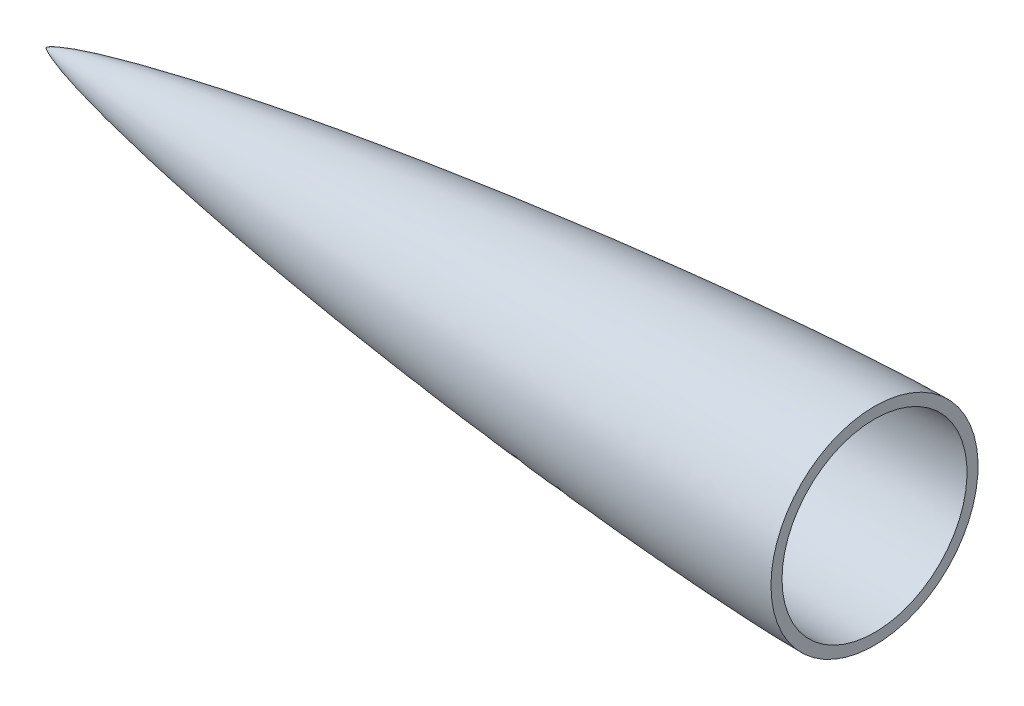
SolidWorks part; units mm, degrees
material "Rocket Fibreglass"
ref_plane "Front Plane" through (0, 0, 0) normal (0, 0, 1) x (1, 0, 0)
ref_plane "Top Plane" through (0, 0, 0) normal (0, 1, 0) x (1, 0, 0)
ref_plane "Right Plane" through (0, 0, 0) normal (1, 0, 0) x (0, 0, -1)
sketch "Sketch3" plane through (0, 0, 0) normal (0, 0, 1) x (1, 0, 0)
  line L0 (0, 0) -> (300, 0)
  line L1 (300, 0) -> (300, 37.5)
  spline S0 degree 4 poles (0, 0) (0.002, 0.0062) (0.0071, 0.018) (0.0217, 0.0396) (0.0552, 0.0792) (0.1042, 0.126) (0.1683, 0.1794) (0.2608, 0.2488) (0.3875, 0.3348) (0.5786, 0.4525) (0.8976, 0.6294) (1.4369, 0.8968) (2.3828, 1.3116) (4.1054, 1.9738) (7.2631, 3.0257) (12.5834, 4.553) (22.0321, 6.9012) (35.261, 9.7168) (51.552, 12.7665) (70.0747, 15.8613) (88.64, 18.6862) (107.238, 21.2875) (125.8618, 23.695) (144.5076, 25.9261) (163.1724, 27.9917) (181.8544, 29.8967) (200.5519, 31.6418) (219.264, 33.2227) (237.9901, 34.629) (256.7298, 35.8427) (272.6842, 36.6821) (284.9023, 37.1716) (293.3782, 37.4059) (297.1619, 37.4748) (299.0539, 37.4972) (300, 37.5) knots 0 0 0 0 0 0.000085 0.000171 0.000342 0.000683 0.000977 0.001272 0.001867 0.002703 0.003938 0.006082 0.009808 0.016327 0.028282 0.049986 0.082826 0.144772 0.206717 0.268663 0.330609 0.392555 0.4545 0.516446 0.578392 0.640337 0.702283 0.764229 0.826175 0.88812 0.950066 0.975033 0.987517 1 1 1 1 1 construction
  spline S1 degree 4 poles (0, 0) (0.002, 0.0062) (0.0071, 0.018) (0.0217, 0.0396) (0.0552, 0.0792) (0.1042, 0.126) (0.1683, 0.1794) (0.2608, 0.2488) (0.3875, 0.3348) (0.5786, 0.4525) (0.8976, 0.6294) (1.4369, 0.8968) (2.3828, 1.3116) (4.1054, 1.9738) (7.2631, 3.0257) (12.5834, 4.553) (22.0321, 6.9012) (35.261, 9.7168) (51.552, 12.7665) (70.0747, 15.8613) (88.64, 18.6862) (107.238, 21.2875) (125.8618, 23.695) (144.5076, 25.9261) (163.1724, 27.9917) (181.8544, 29.8967) (200.5519, 31.6418) (219.264, 33.2227) (237.9901, 34.629) (256.7298, 35.8427) (272.6842, 36.6821) (284.9023, 37.1716) (293.3782, 37.4059) (297.1619, 37.4748) (299.0539, 37.4972) (300, 37.5) knots 0 0 0 0 0 0.000085 0.000171 0.000342 0.000683 0.000977 0.001272 0.001867 0.002703 0.003938 0.006082 0.009808 0.016327 0.028282 0.049986 0.082826 0.144772 0.206717 0.268663 0.330609 0.392555 0.4545 0.516446 0.578392 0.640337 0.702283 0.764229 0.826175 0.88812 0.950066 0.975033 0.987517 1 1 1 1 1
revolve "Revolve1" add sketch "Sketch3" angle 360 about L0
shell "Shell3" thickness 4 removed face at (300, 0, 37.5)
